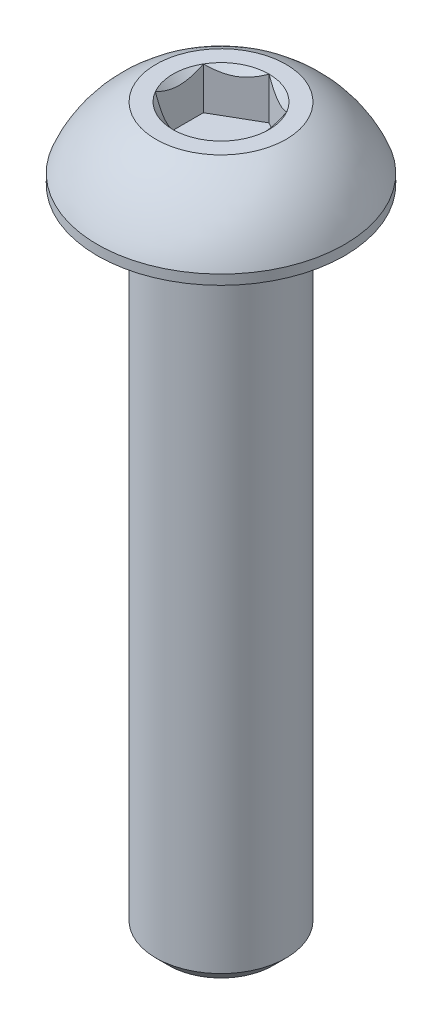
SolidWorks part; units mm, degrees
ref_plane "Front Plane" through (0, 0, 0) normal (0, 0, 1) x (1, 0, 0)
ref_plane "Top Plane" through (0, 0, 0) normal (0, 1, 0) x (1, 0, 0)
ref_plane "Right Plane" through (0, 0, 0) normal (1, 0, 0) x (0, 0, -1)
sketch "Sketch1" plane through (0, 0, 0) normal (0, 1, 0) x (1, 0, 0)
  circle A0 centre (0, 0) radius 2
  dimension "D1" = 4
extrude "Boss-Extrude1" add sketch "Sketch1" against normal blind 20
chamfer "Chamfer1" distance 0.4 angle 45 1 edges at (0, -20, 2)
sketch "Sketch2" plane through (0, 0, 0) normal (0, 1, 0) x (1, 0, 0)
  circle A0 centre (0, 0) radius 3.8
  dimension "D1" = 7.6
extrude "Boss-Extrude2" add sketch "Sketch2" along normal blind 2.2
sketch "Sketch3" plane through (0, 0, 0) normal (0, 0, 1) x (1, 0, 0)
  line L0 (-3.8, 2.2) -> (-3.8, 0) construction
  line L1 (3.8, 2.2) -> (-3.8, 2.2) construction
  line L2 (-2, 2.2) -> (-2, 2.7)
  line L3 (-2, 2.7) -> (-4.3, 2.7)
  line L4 (-4.3, 2.7) -> (-4.3, 0.3)
  line L5 (-4.3, 0.3) -> (-3.8, 0.3)
  line L6 (-3.8, 0) -> (3.8, 0) construction
  line L7 (0, 0) -> (0, 2.2) construction
  arc A0 (-3.8, 0.3) -> (-2, 2.2) centre (-0.5434, -0.9825) cw
  dimension "D5" = 3.5
  dimension "D1" = 0.3
  dimension "D2" = 2
  dimension "D3" = 0.5
  dimension "D4" = 0.5
revolve "Cut-Revolve1" cut sketch "Sketch3" angle 360 about L7
sketch "Sketch4" plane through (0, 2.2, 0) normal (0, 1, 0) x (1, 0, 0)
  line L1 (0, 1.478) -> (-1.28, 0.739)
  line L2 (-1.28, 0.739) -> (-1.28, -0.739)
  line L3 (-1.28, -0.739) -> (0, -1.478)
  line L4 (0, -1.478) -> (1.28, -0.739)
  line L5 (1.28, -0.739) -> (1.28, 0.739)
  line L6 (1.28, 0.739) -> (0, 1.478)
  circle A0 centre (0, 0) radius 1.28 construction
  dimension "D1" = 2.56
extrude "Cut-Extrude1" cut sketch "Sketch4" against normal blind 1.3
sketch "Sketch5" plane through (0, 2.2, 0) normal (0, 1, 0) x (1, 0, 0)
  circle A0 centre (0, 0) radius 1.478
extrude "Cut-Extrude2" cut sketch "Sketch5" against normal blind 1 draft 45
